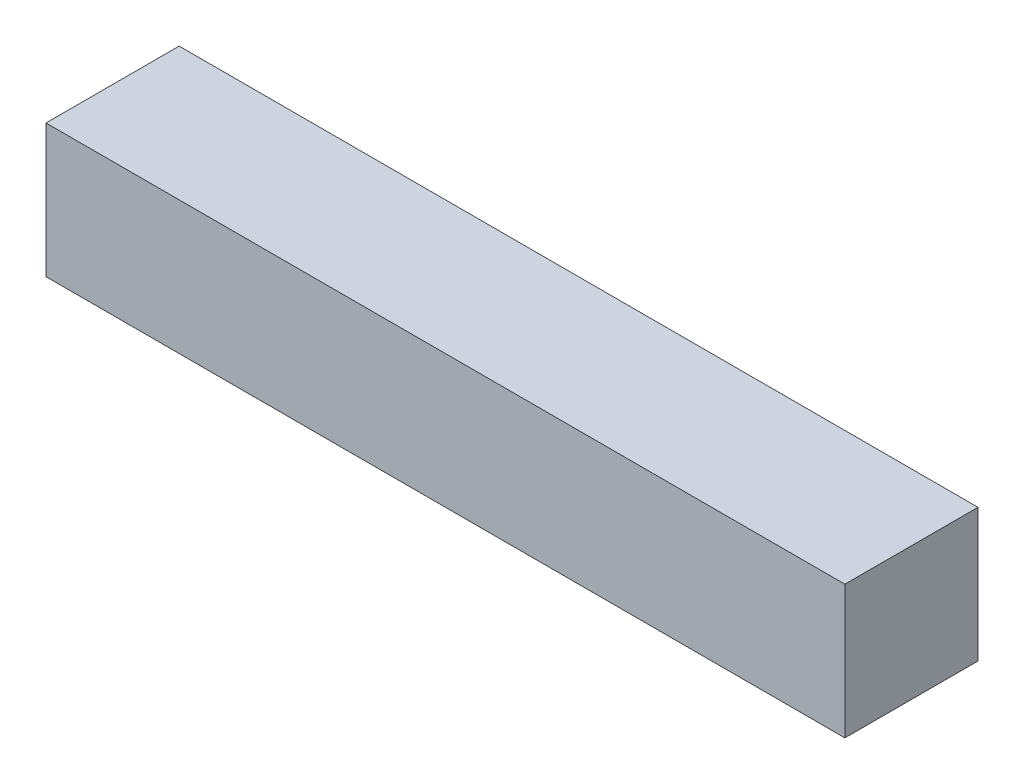
SolidWorks part; units mm, degrees
ref_plane "Front Plane" through (0, 0, 0) normal (0, 0, 1) x (1, 0, 0)
ref_plane "Top Plane" through (0, 0, 0) normal (0, 1, 0) x (1, 0, 0)
ref_plane "Right Plane" through (0, 0, 0) normal (1, 0, 0) x (0, 0, -1)
sketch "Sketch1" plane through (0, 0, 0) normal (1, 0, 0) x (0, 0, -1)
  line L1 (-3.175, -3.175) -> (3.175, -3.175)
  line L2 (-3.175, -3.175) -> (-3.175, 3.175)
  line L3 (-3.175, 3.175) -> (3.175, 3.175)
  line L4 (3.175, -3.175) -> (3.175, 3.175)
  line L5 (-3.175, -3.175) -> (3.175, 3.175) construction
  line L6 (-3.175, 3.175) -> (3.175, -3.175) construction
  point P0 (0, 0)
  dimension "D1" = 6.35
extrude "Boss-Extrude1" add sketch "Sketch1" along normal blind 38.1
ref_axis "Axis1" through (0, 0, 0) along (1, 0, 0)
